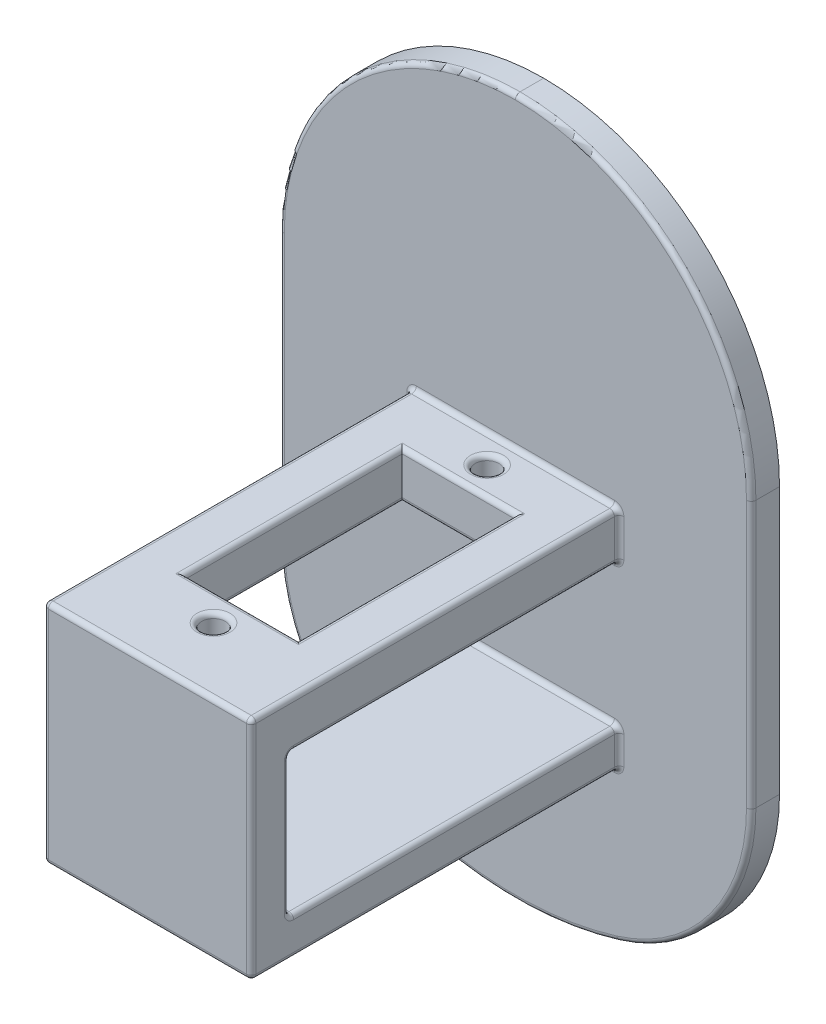
SolidWorks part; units mm, degrees
ref_plane "Front Plane" through (0, 0, 0) normal (0, 0, 1) x (1, 0, 0)
ref_plane "Top Plane" through (0, 0, 0) normal (0, 1, 0) x (1, 0, 0)
ref_plane "Right Plane" through (0, 0, 0) normal (1, 0, 0) x (0, 0, -1)
sketch "Sketch1" plane through (0, 0, 0) normal (0, 0, 1) x (1, 0, 0)
  circle A0 centre (0, 0) radius 37
  point P0 (0, 0)
  dimension "D1" = 74
extrude "Boss-Extrude1" add sketch "Sketch1" along normal blind 3
sketch "Sketch10" plane through (0, 0, 3) normal (0, 0, 1) x (1, 0, 0)
  line L0 (-25, 27.2764) -> (-25, -27.2764)
  line L2 (25, -27.2764) -> (25, 27.2764)
  circle A0 centre (0, 0) radius 37 construction
  arc A1 (-25, 27.2764) -> (-25, -27.2764) centre (0, 0) ccw
  circle A2 centre (0, 0) radius 37
  arc A3 (25, -27.2764) -> (25, 27.2764) centre (0, 0) ccw
  dimension "D2" = 25
  dimension "D3" = 50
  dimension "D1" = 0
extrude "Cut-Extrude3" cut sketch "Sketch10" against normal blind 10
fillet "Fillet1" radius 25 2 edges at (-25, 27.2764, 1.5) (25, 27.2764, 1.5)
fillet "Fillet2" radius 20 2 edges at (-25, -27.2764, 1.5) (25, -27.2764, 1.5)
sketch "Sketch4" plane through (0, 0, 3) normal (0, 0, 1) x (1, 0, 0)
  line L1 (-11, 4.5) -> (11, 4.5)
  line L2 (-11, 4.5) -> (-11, -0.5)
  line L3 (-11, -0.5) -> (11, -0.5)
  line L4 (11, 4.5) -> (11, -0.5)
  line L5 (-11, 4.5) -> (11, -0.5) construction
  line L6 (-11, -0.5) -> (11, 4.5) construction
  point P0 (0, 2)
  dimension "D1" = 22
  dimension "D2" = 5
  dimension "D3" = 2
extrude "Boss-Extrude2" add sketch "Sketch4" along normal blind 35
sketch "Sketch5" plane through (0, 4.5, 0) normal (0, 1, 0) x (1, 0, 0)
  line L1 (-6, -9) -> (6, -9)
  line L2 (-6, -9) -> (-6, -32)
  line L3 (-6, -32) -> (6, -32)
  line L4 (6, -9) -> (6, -32)
  line L5 (-6, -9) -> (6, -32) construction
  line L6 (-6, -32) -> (6, -9) construction
  line L7 (-11, -38) -> (-11, -3) construction
  line L8 (11, -38) -> (-11, -38) construction
  point P0 (0, -20.5)
  point P10 (-11, -20.5)
  point P12 (0, -38)
  dimension "D1" = 12
  dimension "D2" = 23
extrude "Cut-Extrude1" cut sketch "Sketch5" against normal blind 5
sketch "Sketch6" plane through (0, 4.5, 0) normal (0, 1, 0) x (1, 0, 0)
  line L0 (0, -6) -> (0, -35) construction
  line L1 (-6, -9) -> (-6, -32) construction
  line L2 (-6, -32) -> (6, -32) construction
  circle A0 centre (0, -6) radius 1.25
  circle A1 centre (0, -35) radius 1.25
  point P4 (0, -20.5)
  point P7 (-6, -20.5)
  point P10 (0, -32)
  dimension "D1" = 2.5
  dimension "D2" = 29
extrude "Cut-Extrude2" cut sketch "Sketch6" against normal blind 5
sketch "Sketch7" plane through (0, 0, 38) normal (0, 0, 1) x (1, 0, 0)
  line L0 (11, -0.5) -> (11, 4.5) construction
  line L1 (-11, 4.5) -> (11, 4.5)
  line L2 (-11, 4.5) -> (-11, -15.5)
  line L3 (-11, -15.5) -> (11, -15.5)
  line L4 (11, 4.5) -> (11, -15.5)
  line L5 (11, -0.5) -> (11, 4.5) construction
  dimension "D1" = 20
extrude "Boss-Extrude3" add sketch "Sketch7" along normal blind 4
sketch "Sketch8" plane through (0, -15.5, 0) normal (0, -1, 0) x (1, 0, 0)
  line L1 (-11, 42) -> (11, 42)
  line L2 (-11, 42) -> (-11, 3)
  line L3 (-11, 3) -> (11, 3)
  line L4 (11, 42) -> (11, 3)
extrude "Boss-Extrude4" add sketch "Sketch8" along normal blind 4
sketch "Sketch9" plane through (0, -19.5, 0) normal (0, -1, 0) x (1, 0, 0)
  line L0 (-11, 3) -> (11, 3) construction
  circle A0 centre (0, 25.5) radius 3.75
  dimension "D1" = 7.5
  dimension "D2" = 22.5
extrude "Boss-Extrude5" add sketch "Sketch9" along normal blind 7
fillet "Fillet3" radius 0.5 45 edges at (11, -8, 38) (-11, -8, 38) (0, -26.5, 21.75) (11, -19.5, 22.5) (-11, -19.5, 22.5) (0, -19.5, 21.75) (-11, -0.5, 20.5) (0, -0.5, 38) (11, -0.5, 20.5) (-6, -0.5, 20.5) (0, -0.5, 9) (6, -0.5, 20.5) (0, -0.5, 32) (0, -0.5, 36.25) (0, -0.5, 7.25) (11, -15.5, 20.5) (0, -15.5, 38) (-11, -15.5, 20.5) (11, -7.5, 42) (0, -19.5, 42) (-11, -7.5, 42) (11, 4.5, 22.5) (0, 4.5, 42) (-11, 4.5, 22.5) (-6, 4.5, 20.5) (0, 4.5, 32) (6, 4.5, 20.5) (0, 4.5, 9) (0, 4.5, 36.25) (0, 4.5, 7.25) (-11, 2, 3) (0, -0.5, 3) (11, 2, 3) (0, 4.5, 3) (-17.6777, 29.6777, 3) (17.6777, 29.6777, 3) (25, -2.124, 3) (21.088, -28.1298, 3) (0, -37, 3) (-21.088, -28.1298, 3) (-25, -2.124, 3) (11, -17.5, 3) (0, -15.5, 3) (-11, -17.5, 3) (0, -19.5, 3)
